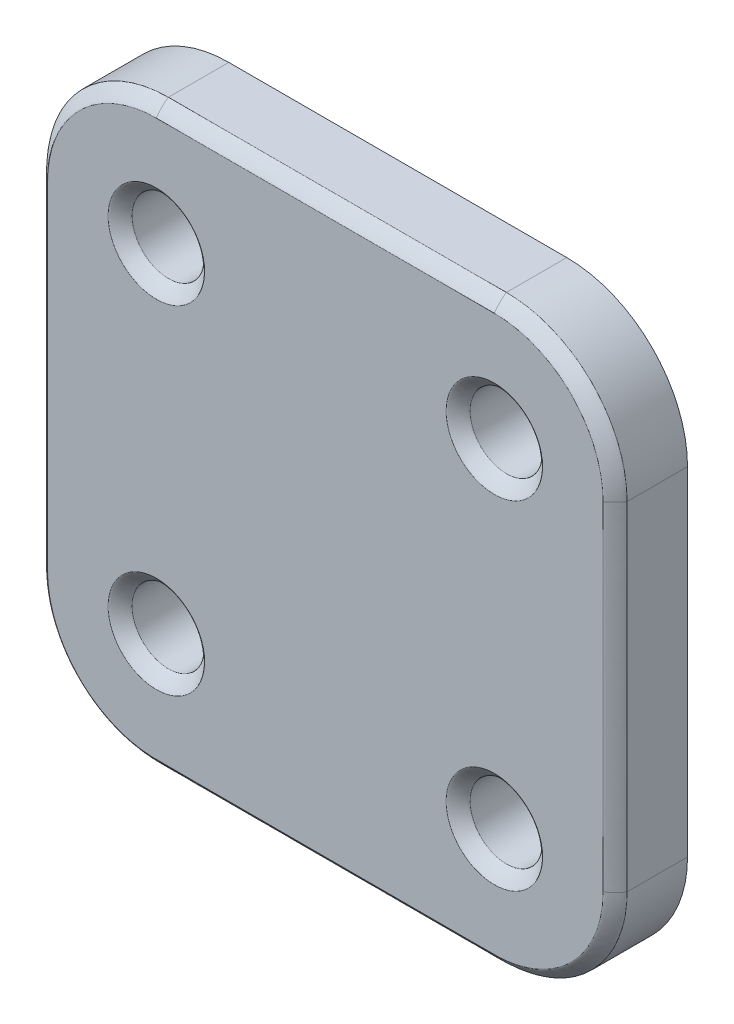
SolidWorks part; units mm, degrees
ref_plane "Plan de face" through (0, 0, 0) normal (0, 0, 1) x (1, 0, 0)
ref_plane "Plan de dessus" through (0, 0, 0) normal (0, 1, 0) x (1, 0, 0)
ref_plane "Plan de droite" through (0, 0, 0) normal (1, 0, 0) x (0, 0, -1)
sketch "Esquisse1" plane through (0, 0, 0) normal (0, 0, 1) x (1, 0, 0)
  line L0 (-7, 7) -> (7, 7) construction
  line L1 (7, -12) -> (-7, -12)
  line L2 (12, -7) -> (12, 7)
  line L3 (7, 12) -> (-7, 12)
  line L4 (-12, -7) -> (-12, 7)
  line L5 (12, -12) -> (-12, 12) construction
  line L6 (12, 12) -> (-12, -12) construction
  line L7 (-7, -7) -> (-7, 7) construction
  arc A0 (-7, -12) -> (-12, -7) centre (-7, -7) cw
  arc A1 (7, -12) -> (12, -7) centre (7, -7) ccw
  arc A2 (12, 7) -> (7, 12) centre (7, 7) ccw
  arc A3 (-7, 12) -> (-12, 7) centre (-7, 7) ccw
  circle A5 centre (-7, 7) radius 1.5
  circle A6 centre (7, 7) radius 1.5
  circle A7 centre (7, -7) radius 1.5
  circle A8 centre (-7, -7) radius 1.5
  point P0 (0, 0)
  dimension "D2" = 5
  dimension "D3" = 3
  dimension "D1" = 14
  dimension "D6" = 14
  dimension "D7" = 14
  dimension "D4" = 2
  dimension "D5" = 2
extrude "Boss.-Extru.1" add sketch "Esquisse1" along normal blind 3
sketch "Esquisse2" plane through (0, 0, 0) normal (0, 0, -1) x (-1, 0, 0)
  circle A0 centre (0, 0) radius 4.1
  dimension "D1" = 8.2
extrude "Enlèv. mat.-Extru.1" cut sketch "Esquisse2" against normal blind 1
fillet "Congé1" radius 0.5 13 edges at (-5.5, -7, 3) (8.5, -7, 3) (8.5, 7, 3) (-5.5, 7, 3) (-12, 0, 3) (-10.5355, 10.5355, 3) (0, 12, 3) (10.5355, 10.5355, 3) (12, 0, 3) (10.5355, -10.5355, 3) (0, -12, 3) (-10.5355, -10.5355, 3) (-4.1, 0, 0) conic rho 0.1
